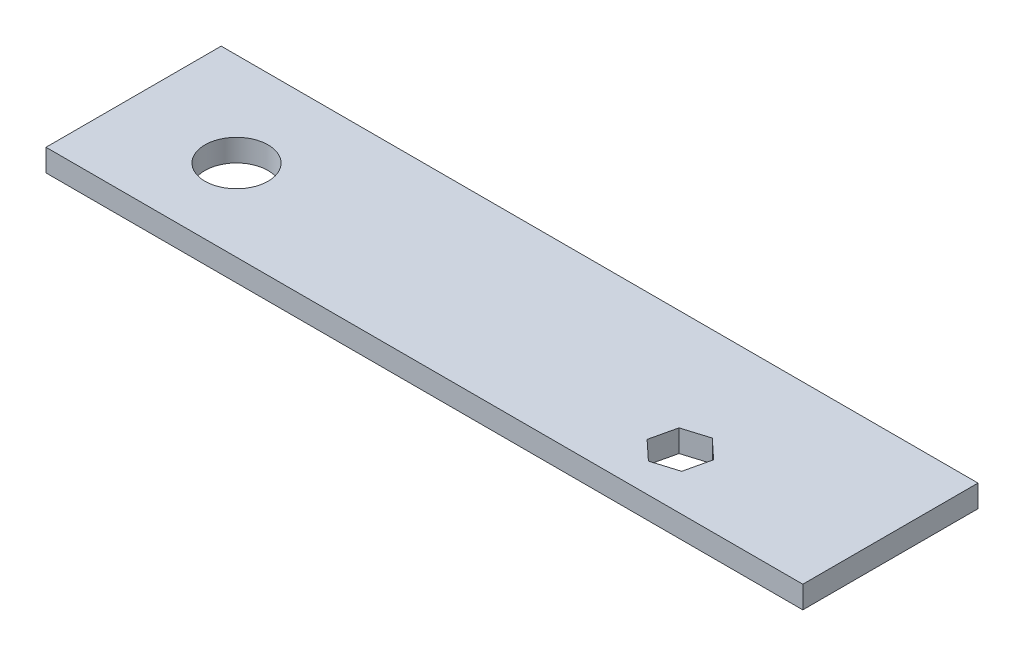
SolidWorks part; units mm, degrees
ref_plane "Front" through (0, 0, 0) normal (0, 0, 1) x (1, 0, 0)
ref_plane "Top" through (0, 0, 0) normal (0, 1, 0) x (1, 0, 0)
ref_plane "Right" through (0, 0, 0) normal (1, 0, 0) x (0, 0, -1)
sketch "Sketch1" plane through (0, 0, 0) normal (0, 1, 0) x (1, 0, 0)
  line L1 (0, 0) -> (108, 0)
  line L2 (0, 0) -> (0, 25)
  line L3 (0, 25) -> (108, 25)
  line L4 (108, 0) -> (108, 25)
  line L5 (86.2599, 9.0113) -> (83.4793, 11.602)
  line L6 (83.4793, 11.602) -> (79.8454, 10.4893)
  line L7 (79.8454, 10.4893) -> (78.9921, 6.7859)
  line L8 (78.9921, 6.7859) -> (81.7727, 4.1952)
  line L9 (81.7727, 4.1952) -> (85.4065, 5.3079)
  line L10 (85.4065, 5.3079) -> (86.2599, 9.0113)
  circle A1 centre (15.5424, 11.6447) radius 4.5
  circle A2 centre (82.626, 7.8986) radius 3.2912 construction
  dimension "D1" = 108
  dimension "D2" = 25
extrude "Boss-Extrude1" add sketch "Sketch1" along normal blind 3.175
